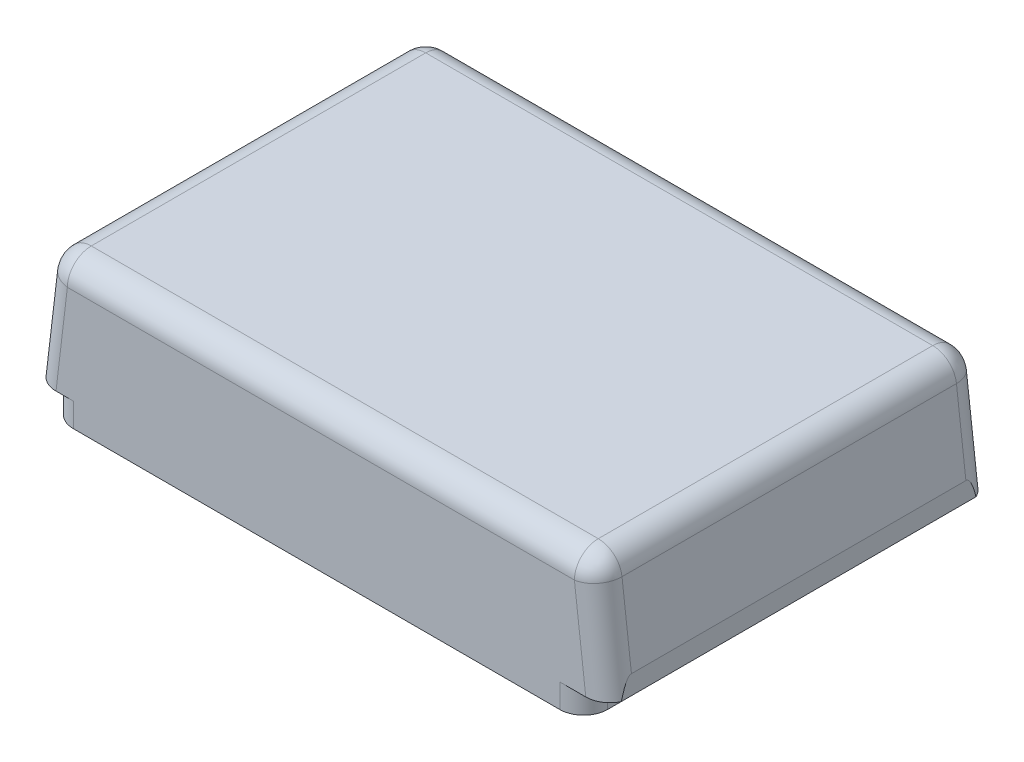
SolidWorks part; units mm, degrees
ref_plane "Front Plane" through (0, 0, 0) normal (0, 0, 1) x (1, 0, 0)
ref_plane "Top Plane" through (0, 0, 0) normal (0, 1, 0) x (1, 0, 0)
ref_plane "Right Plane" through (0, 0, 0) normal (1, 0, 0) x (0, 0, -1)
sketch "Sketch3" plane through (0, 0, 0) normal (0, 0, 1) x (1, 0, 0)
  line L0 (-120, 0) -> (120, 0) construction
  line L1 (-115, 42) -> (-120, 0)
  line L2 (-120, 0) -> (-120, -8)
  line L3 (-120, -8) -> (-113.6471, -8)
  line L4 (-113.6471, -8) -> (-113.6471, -18)
  line L5 (-113.6471, -18) -> (110, -18)
  line L6 (110, -18) -> (110, -8)
  line L7 (110, -8) -> (120, -8)
  line L8 (120, -8) -> (120, 0)
  line L9 (120, 0) -> (115, 42)
  line L10 (115, 42) -> (-115, 42)
  line L11 (0, 130.2353) -> (0, -116.8235) construction
  dimension "D1" = 240
  dimension "D2" = 120
  dimension "D3" = 10
  dimension "D4" = 6.3529
  dimension "D5" = 10
  dimension "D6" = 8
  dimension "D7" = 8
  dimension "D8" = 42
  dimension "D9" = 60
  dimension "D10" = 230
  dimension "D11" = 115
extrude "Boss-Extrude1" add sketch "Sketch3" along normal blind 160
fillet "Fillet5" radius 10 3 edges at (117.5, 21, 0) (-117.5, 21, 160) (-117.5, 21, 0)
fillet "Fillet6" radius 10 1 edges at (117.5, 21, 160)
fillet "Fillet7" radius 10 3 edges at (-113.6471, -12.9665, 159.7642) (110, -13, 0) (110, -13, 160)
fillet "Fillet8" radius 10 1 edges at (-113.6471, -12.9665, 0.2358)
fillet "Fillet9" radius 10 8 edges at (112.0504, 42, 157.0711) (115, 42, 80) (112.0504, 42, 2.9289) (0, 42, 0) (-112.0504, 42, 2.9289) (-115, 42, 80) (-112.0504, 42, 157.0711) (0, 42, 160)
